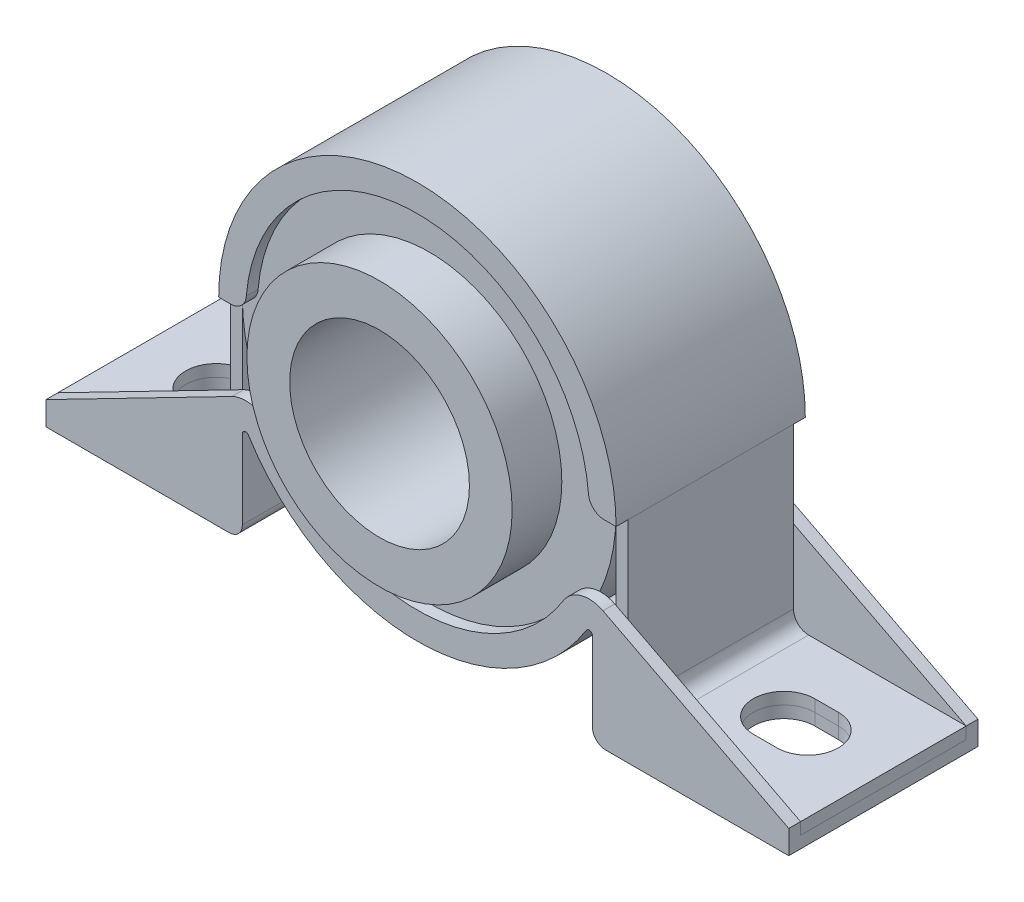
SolidWorks part; units mm, degrees
ref_plane "Front" through (0, 0, 0) normal (0, 0, 1) x (1, 0, 0)
ref_plane "Top" through (0, 0, 0) normal (0, 1, 0) x (1, 0, 0)
ref_plane "Right" through (0, 0, 0) normal (1, 0, 0) x (0, 0, -1)
sketch "Sketch1" plane through (0, 0, 0) normal (0, 0, 1) x (1, 0, 0)
  line L1 (-35.8775, -29.3687) -> (-62.3094, -29.3687) construction
  line L2 (-62.3094, -29.3687) -> (-62.3094, -33.3375) construction
  line L3 (-62.3094, -33.3375) -> (62.3094, -33.3375) construction
  line L6 (0, 0) -> (0, -33.3375) construction
  line L9 (62.3094, -33.3375) -> (62.3094, -29.3688) construction
  line L10 (62.3094, -29.3688) -> (35.8775, -29.3687) construction
  line L12 (-33.3375, 0) -> (-33.3375, -26.8287) construction
  line L13 (-62.3094, -31.3531) -> (-31.3531, -31.3531)
  line L14 (33.3375, 0) -> (33.3375, -26.8287) construction
  line L15 (-31.3531, -31.3531) -> (-31.3531, -17.8479)
  line L16 (31.3531, -17.8479) -> (31.3531, -31.3531)
  line L17 (31.3531, -31.3531) -> (62.3094, -31.3531)
  circle A0 centre (0, 0) radius 15.0813 construction
  circle A1 centre (0, 0) radius 22.2504 construction
  arc A2 (33.3375, 0) -> (-33.3375, 0) centre (0, 0) ccw construction
  arc A5 (-33.3375, -26.8287) -> (-35.8775, -29.3687) centre (-35.8775, -26.8287) cw construction
  arc A6 (33.3375, -26.8287) -> (35.8775, -29.3687) centre (35.8775, -26.8287) ccw construction
  arc A7 (-31.3531, -17.8479) -> (-26.6538, -16.5104) centre (-28.8131, -17.8479) cw
  arc A8 (-26.6538, -16.5104) -> (26.6538, -16.5104) centre (0, 0) ccw
  arc A9 (26.6538, -16.5104) -> (31.3531, -17.8479) centre (28.8131, -17.8479) cw
  dimension "Shaft Dia" = 30.1625
  dimension "K" = 44.5008
  dimension "D1" = 2.54
  dimension "w" = 66.675
  dimension "h" = 33.3375
  dimension "g" = 3.9688
  dimension "a" = 124.6188
  dimension "D2" = 1.9844
extrude "Extrude-Thin2" add sketch "Sketch1" along normal mid plane 31.75 thin thin type one direction wall 1.9844
sketch "Sketch4" plane through (0, 0, 15.875) normal (0, 0, 1) x (1, 0, 0)
  line L0 (-62.3094, -29.3687) -> (-31.1372, -13.3307)
  line L1 (31.1372, -13.3307) -> (62.3094, -29.3688)
  line L2 (-35.8775, -29.3687) -> (-62.3094, -29.3687) construction
  line L3 (62.3094, -29.3688) -> (35.8775, -29.3688) construction
  line L10 (31.6071, -33.3375) -> (62.3094, -33.3375)
  line L11 (62.3094, -33.3375) -> (62.3094, -31.3531)
  line L12 (62.3094, -31.3531) -> (31.6071, -31.3531)
  line L13 (31.3531, -31.0991) -> (31.3531, -17.8479)
  line L14 (-31.3531, -17.8479) -> (-31.3531, -31.0991)
  line L15 (-31.6071, -31.3531) -> (-62.3094, -31.3531)
  line L16 (-62.3094, -31.3531) -> (-62.3094, -33.3375)
  line L17 (-62.3094, -33.3375) -> (-31.6071, -33.3375)
  line L18 (-29.3687, -31.0991) -> (-29.3687, -17.8479)
  line L19 (29.3687, -17.8479) -> (29.3687, -31.0991)
  line L20 (31.6071, -33.3375) -> (62.3094, -33.3375)
  line L21 (62.3094, -33.3375) -> (62.3094, -29.3688)
  line L26 (-62.3094, -29.3687) -> (-62.3094, -33.3375)
  line L27 (-62.3094, -33.3375) -> (-31.6071, -33.3375)
  line L28 (-29.3687, -31.0991) -> (-29.3687, -17.8479)
  line L29 (29.3687, -17.8479) -> (29.3687, -31.0991)
  arc A0 (-24.4945, -15.1728) -> (-31.1372, -13.3307) centre (-28.8131, -17.8479) ccw
  arc A1 (31.1372, -13.3307) -> (24.4945, -15.1728) centre (28.8131, -17.8479) ccw
  arc A2 (-24.4945, -15.1728) -> (24.4945, -15.1728) centre (0, 0) ccw
  arc A10 (31.3531, -31.0991) -> (31.6071, -31.3531) centre (31.6071, -31.0991) ccw
  arc A11 (31.3531, -17.8479) -> (26.6538, -16.5104) centre (28.8131, -17.8479) ccw
  arc A12 (-26.6538, -16.5104) -> (26.6538, -16.5104) centre (0, 0) ccw
  arc A13 (-26.6538, -16.5104) -> (-31.3531, -17.8479) centre (-28.8131, -17.8479) ccw
  arc A14 (-31.6071, -31.3531) -> (-31.3531, -31.0991) centre (-31.6071, -31.0991) ccw
  arc A15 (-31.6071, -33.3375) -> (-29.3687, -31.0991) centre (-31.6071, -31.0991) ccw
  arc A17 (-28.3408, -17.5553) -> (28.3408, -17.5553) centre (0, 0) ccw
  arc A19 (29.3687, -31.0991) -> (31.6071, -33.3375) centre (31.6071, -31.0991) ccw
  arc A21 (-28.3408, -17.5553) -> (-29.3687, -17.8479) centre (-28.8131, -17.8479) ccw
  arc A22 (-28.3408, -17.5553) -> (-29.3687, -17.8479) centre (-28.8131, -17.8479) ccw
  arc A23 (29.3687, -17.8479) -> (28.3408, -17.5553) centre (28.8131, -17.8479) ccw
  arc A24 (29.3687, -17.8479) -> (28.3408, -17.5553) centre (28.8131, -17.8479) ccw
  arc A25 (-31.6071, -33.3375) -> (-29.3687, -31.0991) centre (-31.6071, -31.0991) ccw
  arc A27 (-28.3408, -17.5553) -> (28.3408, -17.5553) centre (0, 0) ccw
  arc A29 (29.3687, -31.0991) -> (31.6071, -33.3375) centre (31.6071, -31.0991) ccw
  dimension "D2" = 5.08
  dimension "D1" = 0
extrude "Extrude1" add sketch "Sketch4" against normal blind 1.9844
mirror "Mirror1" about plane through (0, 0, 0) normal (0, 0, 1) of "Extrude1"
sketch "Sketch5" plane through (0, 0, 0) normal (0, 0, 1) x (1, 0, 0)
  line L0 (62.3094, -29.3688) -> (35.8775, -29.3687) construction
  line L1 (33.3375, 0) -> (33.3375, -26.8287) construction
  line L2 (-33.3375, 0) -> (-33.3375, -26.8287) construction
  line L3 (-35.8775, -29.3687) -> (-62.3094, -29.3687) construction
  line L4 (62.3094, -29.3688) -> (35.8775, -29.3687)
  line L5 (33.3375, 0) -> (33.3375, -26.8287)
  line L6 (-33.3375, 0) -> (-33.3375, -26.8287)
  line L7 (-35.8775, -29.3687) -> (-62.3094, -29.3687)
  arc A0 (33.3375, -26.8287) -> (35.8775, -29.3687) centre (35.8775, -26.8287) ccw construction
  arc A1 (33.3375, 0) -> (-33.3375, 0) centre (0, 0) ccw construction
  arc A2 (-35.8775, -29.3687) -> (-33.3375, -26.8287) centre (-35.8775, -26.8287) ccw construction
  arc A3 (33.3375, -26.8287) -> (35.8775, -29.3687) centre (35.8775, -26.8287) ccw
  arc A4 (33.3375, 0) -> (-33.3375, 0) centre (0, 0) ccw
  arc A5 (-35.8775, -29.3687) -> (-33.3375, -26.8287) centre (-35.8775, -26.8287) ccw
extrude "Extrude-Thin3" add sketch "Sketch5" along normal up to surface (13.8906 mm away) and the other way up to surface (13.8906 mm away) separate body thin up to face at (0, -24.6571, 13.8906) other way up to face at (0, -24.6571, -13.8906) thin type one direction reverse wall 1.9844
sketch "Sketch6" plane through (0, 0, -13.8906) normal (0, 0, -1) x (-1, 0, 0)
  line L0 (-33.3375, 0) -> (33.3375, 0) construction
  line L1 (-31.3531, 0) -> (-33.3375, 0)
  line L2 (33.3375, 0) -> (31.3531, 0)
  arc A0 (33.3375, 0) -> (-33.3375, 0) centre (0, 0) ccw construction
  arc A1 (33.3375, 0) -> (-33.3375, 0) centre (0, 0) ccw
  arc A2 (-24.4945, -15.1728) -> (24.4945, -15.1728) centre (0, 0) ccw construction
  arc A3 (-24.4945, -15.1728) -> (28.8131, 0) centre (0, 0) ccw construction
  arc A4 (28.7106, 2.4284) -> (-28.7106, 2.4284) centre (0, 0) ccw
  arc A5 (31.3531, 0) -> (-31.3531, 0) centre (0, 0) ccw construction
  arc A6 (31.3531, 0) -> (-31.3531, 0) centre (0, 0) ccw construction
  arc A7 (-31.3531, 0) -> (-28.7106, 2.4284) centre (-31.3531, 2.652) ccw
  arc A8 (31.3531, 0) -> (28.7106, 2.4284) centre (31.3531, 2.652) cw
extrude "Extrude2" add sketch "Sketch6" along normal blind 1.9844
mirror "Mirror2" about plane through (0, 0, 0) normal (0, 0, 1) of "Extrude2"
sketch "Sketch7" plane through (0, 0, 0) normal (0, 0, 1) x (1, 0, 0)
  circle A0 centre (0, 0) radius 31.3531
  circle A1 centre (0, 0) radius 22.2504
  circle A2 centre (0, 0) radius 22.2504 construction
  arc A3 (-26.6538, -16.5104) -> (26.6538, -16.5104) centre (0, 0) ccw construction
extrude "Extrude3" add sketch "Sketch7" along normal up to surface (13.8906 mm away) and the other way up to surface (13.8906 mm away) separate body up to face at (0, -24.6571, 13.8906) other way up to face at (0, -24.6571, -13.8906)
ref_plane "Plane1" through (0, 0, 22.225) normal (0, 0, -1) x (-1, 0, 0)
sketch "Sketch8" plane through (0, 0, 22.225) normal (0, 0, 1) x (1, 0, 0)
  circle A0 centre (0, 0) radius 22.2504 construction
  circle A1 centre (0, 0) radius 15.0813 construction
  circle A2 centre (0, 0) radius 22.2504
  circle A3 centre (0, 0) radius 15.0813
extrude "Extrude4" add sketch "Sketch8" against normal blind 30.1625 separate body
sketch "Sketch3" plane through (0, 0, 0) normal (0, 1, 0) x (1, 0, 0)
  line L2 (-49.6094, 0) -> (-45.6406, 0) construction
  line L3 (-45.6406, 0) -> (0, 0) construction
  line L4 (0, 0) -> (45.6406, 0) construction
  line L5 (45.6406, 0) -> (49.6094, 0) construction
  line L6 (-49.6094, 5.1594) -> (-45.6406, 5.1594)
  line L7 (-49.6094, -5.1594) -> (-45.6406, -5.1594)
  line L8 (45.6406, -5.1594) -> (49.6094, -5.1594)
  line L9 (49.6094, 5.1594) -> (45.6406, 5.1594)
  arc A0 (-49.6094, 5.1594) -> (-49.6094, -5.1594) centre (-49.6094, 0) ccw
  arc A1 (-45.6406, 5.1594) -> (-45.6406, -5.1594) centre (-45.6406, 0) cw
  arc A2 (45.6406, 5.1594) -> (45.6406, -5.1594) centre (45.6406, 0) ccw
  arc A3 (49.6094, 5.1594) -> (49.6094, -5.1594) centre (49.6094, 0) cw
  point P13 (47.625, -5.1594)
  point P14 (-47.625, -5.1594)
  dimension "D1" = 95.25
  dimension "Slot Width" = 10.3187
  dimension "Slot Length" = 14.2875
extrude "Cut-Extrude1" cut sketch "Sketch3" against normal through all
sketch "Sketch9" plane through (0, 0, 0) normal (1, 0, 0) x (0, 0, -1)
  line L0 (-22.225, 0) -> (7.9375, 0) construction
  line L1 (7.9375, -15.0813) -> (7.9375, 15.0813) construction
  line L2 (-22.225, 22.2504) -> (-22.225, -22.2504) construction
equation "\"D2@Sketch1\"=\"g@Sketch1\"/2"
equation "\"D5@Extrude-Thin2\"=\"g@Sketch1\"/2"
equation "\"D1@Extrude1\"=\"g@Sketch1\"/2"
equation "\"D5@Extrude-Thin3\" = \"g@Sketch1\"/2"
equation "\"D1@Extrude2\"=\"g@Sketch1\"/2"
